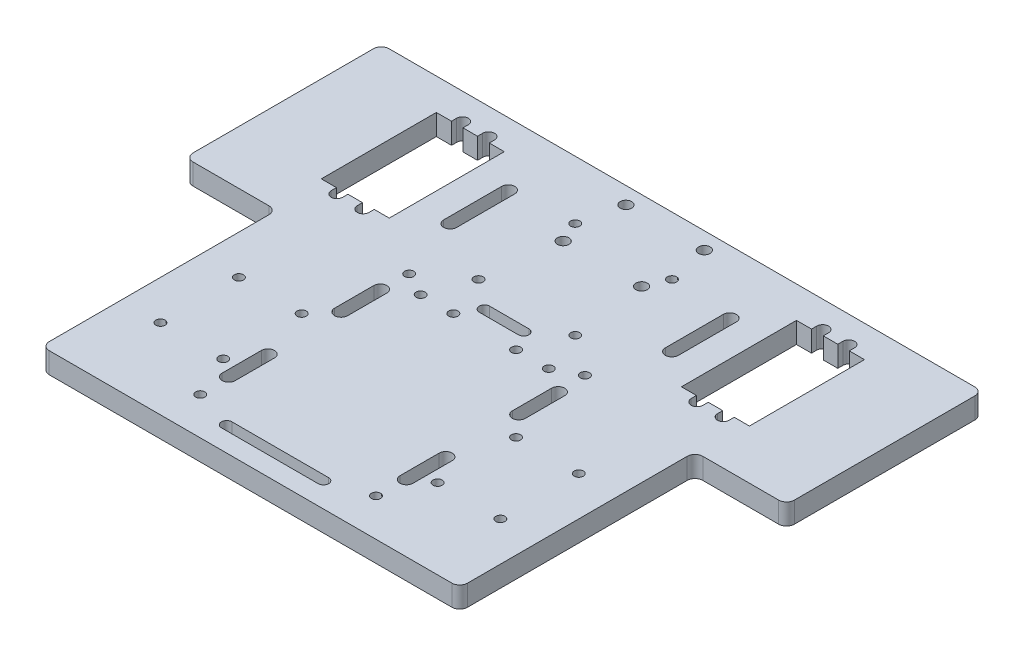
SolidWorks part; units mm, degrees
ref_plane "前视基准面" through (0, 0, 0) normal (0, 0, 1) x (1, 0, 0)
ref_plane "上视基准面" through (0, 0, 0) normal (0, 1, 0) x (1, 0, 0)
ref_plane "右视基准面" through (0, 0, 0) normal (1, 0, 0) x (0, 0, -1)
other "Configuration Table"
sketch "草图1" plane through (0, 0, 0) normal (0, 1, 0) x (1, 0, 0)
  line L1 (115, -130.4648) -> (-115, -130.4648)
  line L2 (115, -130.4648) -> (115, 69.5352)
  line L3 (115, 69.5352) -> (-115, 69.5352)
  line L4 (-115, -130.4648) -> (-115, 69.5352)
  line L5 (115, -130.4648) -> (-115, 69.5352) construction
  line L6 (115, 69.5352) -> (-115, -130.4648) construction
  point P0 (0, -30.4648)
  dimension "D1" = 230
  dimension "D2" = 200
extrude "凸台-拉伸1" add sketch "草图1" along normal blind 8
sketch "草图2" plane through (0, 0, 0) normal (0, 1, 0) x (1, 0, 0)
  line L0 (0, 0) -> (0, -142.6285) construction
  line L1 (33.6, -116.0917) -> (-33.6, -116.0917)
  line L2 (33.6, -116.0917) -> (33.6, -36.1917)
  line L3 (33.6, -36.1917) -> (-33.6, -36.1917)
  line L4 (-33.6, -116.0917) -> (-33.6, -36.1917)
  line L5 (33.6, -116.0917) -> (-33.6, -36.1917) construction
  line L6 (33.6, -36.1917) -> (-33.6, -116.0917) construction
  line L7 (-80, -130.4648) -> (-115, -130.4648)
  line L12 (-80, -130.4648) -> (-80, -40.4648)
  line L13 (-115, -130.4648) -> (-115, -40.4648)
  line L14 (-65, -69.9176) -> (-41, -69.9176)
  line L15 (0, -40.8981) -> (-12, -40.8981)
  line L16 (-12, -40.8981) -> (-24.5, -40.8981)
  line L17 (-73.8742, 24.4667) -> (-73.8742, -23.5333) construction
  line L18 (18.5, -24.7805) -> (-18.5, -24.7805)
  line L19 (18.5, -24.7805) -> (18.5, 12.2195)
  line L20 (18.5, 12.2195) -> (-18.5, 12.2195)
  line L21 (-18.5, -24.7805) -> (-18.5, 12.2195)
  line L22 (18.5, -24.7805) -> (-18.5, 12.2195) construction
  line L23 (18.5, 12.2195) -> (-18.5, -24.7805) construction
  line L24 (-55.8742, -21.5333) -> (-81.8742, -21.5333)
  line L25 (-55.8742, -21.5333) -> (-55.8742, 22.4667)
  line L26 (-55.8742, 22.4667) -> (-81.8742, 22.4667)
  line L27 (-81.8742, -21.5333) -> (-81.8742, 22.4667)
  line L28 (-55.8742, -21.5333) -> (-81.8742, 22.4667) construction
  line L29 (-55.8742, 22.4667) -> (-81.8742, -21.5333) construction
  line L30 (-63.8742, -23.5333) -> (-73.8742, -23.5333)
  line L31 (-63.8742, -23.5333) -> (-63.8742, 24.4667)
  line L32 (-63.8742, 24.4667) -> (-73.8742, 24.4667)
  line L33 (-73.8742, -23.5333) -> (-73.8742, 24.4667)
  line L34 (-63.8742, -23.5333) -> (-73.8742, 24.4667) construction
  line L35 (-63.8742, 24.4667) -> (-73.8742, -23.5333) construction
  line L38 (-71.6742, 24.4667) -> (-71.6742, -23.5333)
  line L41 (55.8742, -21.5333) -> (81.8742, -21.5333)
  line L42 (55.8742, -21.5333) -> (55.8742, 22.4667)
  line L43 (55.8742, 22.4667) -> (81.8742, 22.4667)
  line L44 (81.8742, -21.5333) -> (81.8742, 22.4667)
  line L45 (63.8742, 24.4667) -> (63.8742, -23.5333) construction
  line L48 (61.6242, 24.4667) -> (61.6242, -23.5333)
  line L51 (-76.0742, 24.4667) -> (-76.0742, -23.5333)
  line L52 (15, 4.1019) -> (-15, 4.1019)
  line L53 (15, 4.1019) -> (15, 28.1019)
  line L54 (15, 28.1019) -> (-15, 28.1019)
  line L55 (-15, 4.1019) -> (-15, 28.1019)
  line L56 (15, 4.1019) -> (-15, 28.1019) construction
  line L57 (15, 28.1019) -> (-15, 4.1019) construction
  line L60 (-18.5, -121.0937) -> (18.5, -121.0937) construction
  line L61 (-18.5, -119.0937) -> (18.5, -119.0937)
  line L62 (-18.5, -123.0937) -> (18.5, -123.0937)
  line L63 (-63.8742, 24.4667) -> (-63.8742, -23.5333) construction
  line L64 (-61.6242, 24.4667) -> (-61.6242, -23.5333)
  line L65 (-66.1242, 24.4667) -> (-66.1242, -23.5333)
  line L66 (66.1242, 24.4667) -> (66.1242, -23.5333)
  line L67 (73.8742, 24.4667) -> (73.8742, -23.5333) construction
  line L68 (71.6742, 24.4667) -> (71.6742, -23.5333)
  line L69 (76.0742, 24.4667) -> (76.0742, -23.5333)
  line L70 (-80, -40.4648) -> (-115, -40.4648)
  line L71 (-65, -69.9176) -> (-41, -69.9176)
  line L72 (-65, -69.9176) -> (-65, -99.9176)
  line L73 (-41, -69.9176) -> (-41, -99.9176)
  line L74 (-65, -99.9176) -> (-41, -99.9176)
  line L75 (-115, -130.4648) -> (115, -130.4648) construction
  line L76 (80, -130.4648) -> (80, -40.4648)
  line L77 (80, -130.4648) -> (115, -130.4648)
  line L78 (115, -130.4648) -> (115, -40.4648)
  line L79 (80, -40.4648) -> (115, -40.4648)
  circle A0 centre (-33.6, -36.1917) radius 1.75
  circle A1 centre (33.6, -36.1917) radius 1.75
  circle A2 centre (-33.6, -116.0917) radius 1.75
  circle A3 centre (33.6, -116.0917) radius 1.75
  circle A4 centre (-41, -69.9176) radius 1.75
  circle A5 centre (-41, -99.9176) radius 1.75
  circle A6 centre (-65, -99.9176) radius 1.75
  circle A7 centre (-65, -69.9176) radius 1.75
  circle A8 centre (-24.5, -40.8981) radius 1.75
  circle A9 centre (-12, -40.8981) radius 1.75
  circle A10 centre (-18.5, 12.2195) radius 1.75
  circle A11 centre (18.5, 12.2195) radius 1.75
  circle A12 centre (18.5, -24.7805) radius 1.75
  circle A13 centre (-18.5, -24.7805) radius 1.75
  circle A18 centre (24.5, -40.8981) radius 1.75
  circle A19 centre (12, -40.8981) radius 1.75
  circle A20 centre (41, -69.9176) radius 1.75
  circle A21 centre (41, -99.9176) radius 1.75
  circle A22 centre (65, -99.9176) radius 1.75
  circle A23 centre (65, -69.9176) radius 1.75
  circle A28 centre (-15, 28.1019) radius 2.2
  circle A29 centre (-15, 4.1019) radius 2.2
  circle A30 centre (15, 28.1019) radius 2.2
  circle A31 centre (15, 4.1019) radius 2.2
  arc A34 (-18.5, -119.0937) -> (-18.5, -123.0937) centre (-18.5, -121.0937) ccw
  arc A35 (18.5, -123.0937) -> (18.5, -119.0937) centre (18.5, -121.0937) ccw
  arc A36 (-71.6742, 24.4667) -> (-76.0742, 24.4667) centre (-73.8742, 24.4667) ccw
  arc A37 (-76.0742, -23.5333) -> (-71.6742, -23.5333) centre (-73.8742, -23.5333) ccw
  arc A38 (-61.6242, 24.4667) -> (-66.1242, 24.4667) centre (-63.8742, 24.4667) ccw
  arc A39 (-66.1242, -23.5333) -> (-61.6242, -23.5333) centre (-63.8742, -23.5333) ccw
  arc A40 (61.6242, 24.4667) -> (66.1242, 24.4667) centre (63.8742, 24.4667) cw
  arc A41 (66.1242, -23.5333) -> (61.6242, -23.5333) centre (63.8742, -23.5333) cw
  arc A42 (71.6742, 24.4667) -> (76.0742, 24.4667) centre (73.8742, 24.4667) cw
  arc A43 (76.0742, -23.5333) -> (71.6742, -23.5333) centre (73.8742, -23.5333) cw
  point P0 (0, -76.1417)
  point P31 (0, 0)
  point P34 (0, -6.2805)
  point P40 (-68.8742, 0.4667)
  point P49 (0, -6.2805)
  point P52 (-73.8742, 0.4667)
  point P53 (-68.8742, 0.4667)
  point P62 (-63.8742, 0.4667)
  point P85 (63.8742, 0.4667)
  point P92 (73.8742, 0.4667)
  point P97 (0, 16.1019)
  point P106 (0, 0)
  point P108 (0, 0)
  point P110 (0, 0)
  point P111 (0, 0)
  point P112 (0, 0)
  point P113 (0, -121.0937)
  point P121 (0, 0)
  point P122 (0, 0)
  point P123 (0, 0)
  point P124 (0, 0)
  point P125 (0, 0)
  point P126 (0, 0)
  point P127 (0, 0)
  point P128 (0, 0)
  point P129 (0, 0)
  dimension "D3" = 35
  dimension "D6" = 37
  dimension "D8" = 4
  dimension "D13" = 30
  dimension "D15" = 30
  dimension "D1" = 67.2
  dimension "D2" = 79.9
  dimension "D4" = 90
  dimension "D7" = 37
  dimension "D9" = 44
  dimension "D10" = 26
  dimension "D11" = 48
  dimension "D12" = 10
  dimension "D14" = 24
extrude "切除-拉伸2" cut sketch "草图2" along normal blind 8 contours L27 L26 L25 L24 | A28 | A29 | A31 | A30 | L42 L43 L44 L41 | L68 A43 L69 A42 | L48 A41 L66 A40 | A4 | A7 | A6 | A5 | A13 | A12 | A19 | A18 | A11 | A10 | A9 | A8 | A0 | A1 | A2 | A3 | L61 A35 L62 A34 | A21 | A22 | A23 | A20
extrude "切除-拉伸3" cut sketch "草图2<3>" along normal blind 8 contours A36 L51 A37 L38 | A38 L65 A39 L64 | A40 L66 A41 L48 | A42 L69 A43 L68
sketch "草图2<3>" plane through (0, 0, 0) normal (0, 1, 0) x (1, 0, 0) same geometry as "草图2"
sketch "草图3" plane through (0, 0, 0) normal (0, 1, 0) x (1, 0, 0)
  line L0 (-42.3858, 10.4742) -> (-42.3858, -11.7168) construction
  line L1 (-39.8858, 10.4742) -> (-39.8858, -11.7168)
  line L2 (-44.8858, 10.4742) -> (-44.8858, -11.7168)
  line L3 (0, 0) -> (0, -150.4011) construction
  line L4 (42.3858, 10.4742) -> (42.3858, -11.7168) construction
  line L5 (39.8858, 10.4742) -> (39.8858, -11.7168)
  line L6 (44.8858, 10.4742) -> (44.8858, -11.7168)
  line L7 (-34, -104.8187) -> (-34, -89.8187) construction
  line L8 (34, -104.8187) -> (-34, -104.8187)
  line L9 (34, -104.8187) -> (34, -46.8187)
  line L10 (34, -46.8187) -> (-34, -46.8187)
  line L11 (-34, -104.8187) -> (-34, -46.8187)
  line L12 (34, -104.8187) -> (-34, -46.8187) construction
  line L13 (34, -46.8187) -> (-34, -104.8187) construction
  line L14 (-36.5, -104.8187) -> (-36.5, -89.8187)
  line L15 (-31.5, -104.8187) -> (-31.5, -89.8187)
  line L16 (-34, -46.8187) -> (-34, -61.8187) construction
  line L19 (-31.5, -46.8187) -> (-31.5, -61.8187)
  line L20 (-36.5, -46.8187) -> (-36.5, -61.8187)
  line L21 (34, -104.8187) -> (34, -89.8187) construction
  line L22 (36.5, -104.8187) -> (36.5, -89.8187)
  line L23 (31.5, -104.8187) -> (31.5, -89.8187)
  line L24 (34, -46.8187) -> (34, -61.8187) construction
  line L25 (31.5, -46.8187) -> (31.5, -61.8187)
  line L26 (36.5, -46.8187) -> (36.5, -61.8187)
  line L27 (-7.5, -33.5004) -> (7.5, -33.5004) construction
  line L28 (-7.5, -31.5004) -> (7.5, -31.5004)
  line L29 (-7.5, -35.5004) -> (7.5, -35.5004)
  arc A0 (-39.8858, 10.4742) -> (-44.8858, 10.4742) centre (-42.3858, 10.4742) ccw
  arc A1 (-44.8858, -11.7168) -> (-39.8858, -11.7168) centre (-42.3858, -11.7168) ccw
  arc A2 (39.8858, 10.4742) -> (44.8858, 10.4742) centre (42.3858, 10.4742) cw
  arc A3 (44.8858, -11.7168) -> (39.8858, -11.7168) centre (42.3858, -11.7168) cw
  arc A8 (-36.5, -104.8187) -> (-31.5, -104.8187) centre (-34, -104.8187) ccw
  arc A9 (-31.5, -89.8187) -> (-36.5, -89.8187) centre (-34, -89.8187) ccw
  arc A12 (-31.5, -46.8187) -> (-36.5, -46.8187) centre (-34, -46.8187) ccw
  arc A13 (-36.5, -61.8187) -> (-31.5, -61.8187) centre (-34, -61.8187) ccw
  arc A14 (36.5, -104.8187) -> (31.5, -104.8187) centre (34, -104.8187) cw
  arc A15 (31.5, -89.8187) -> (36.5, -89.8187) centre (34, -89.8187) cw
  arc A16 (31.5, -46.8187) -> (36.5, -46.8187) centre (34, -46.8187) cw
  arc A17 (36.5, -61.8187) -> (31.5, -61.8187) centre (34, -61.8187) cw
  arc A18 (-7.5, -31.5004) -> (-7.5, -35.5004) centre (-7.5, -33.5004) ccw
  arc A19 (7.5, -35.5004) -> (7.5, -31.5004) centre (7.5, -33.5004) ccw
  point P2 (-42.3858, -0.6213)
  point P10 (-34, -97.3187)
  point P14 (42.3858, -0.6213)
  point P19 (0, -75.8187)
  point P29 (-34, -54.3187)
  point P36 (34, -97.3187)
  point P42 (34, -54.3187)
  point P48 (0, -33.5004)
  point P53 (-42.9173, 15.6566)
  point P54 (-42.7844, -11.7168)
  point P55 (-42.3858, 10.4742)
  dimension "D1" = 68
  dimension "D2" = 58
extrude "切除-拉伸5" cut sketch "草图3" along normal blind 8 contours L1 A1 L2 A0 | L5 A3 L6 A2
extrude "切除-拉伸6" cut sketch "草图3<5>" along normal blind 8 contours L19 A13 L20 A12 | L25 A17 L26 A16 | L15 A9 L14 A8 | L23 A15 L22 A14
sketch "草图3<5>" plane through (0, 0, 0) normal (0, 1, 0) x (1, 0, 0) same geometry as "草图3"
extrude "切除-拉伸7" cut sketch "草图3<6>" along normal blind 8 contours L29 A19 L28 A18
sketch "草图3<6>" plane through (0, 0, 0) normal (0, 1, 0) x (1, 0, 0) same geometry as "草图3"
extrude "切除-拉伸10" cut sketch "草图2<5>" along normal blind 8 contours L12 L70 L13 L7 | L79 L76 L77 L78 region at (-97.5, 0, 85.4648) region at (97.5, 0, 85.4648)
sketch "草图2<5>" plane through (0, 0, 0) normal (0, 1, 0) x (1, 0, 0) same geometry as "草图2"
sketch "草图4" plane through (0, 0, 0) normal (0, 1, 0) x (1, 0, 0)
  line L0 (-115, 69.5352) -> (-115, 34.5352)
  line L1 (-115, 69.5352) -> (115, 69.5352)
  line L2 (-115, 34.5352) -> (115, 34.5352)
  line L3 (115, 69.5352) -> (115, 34.5352)
  line L4 (-115, 69.5352) -> (-115, -40.4648) construction
  dimension "D1" = 35
  dimension "D2" = 230
extrude "切除-拉伸12" cut sketch "草图4" along normal blind 8 contours L0 L1 L3 L2
fillet "圆角1" radius 3 8 edges at (115, 4, -34.5352) (115, 4, 40.4648) (80, 4, 40.4648) (80, 4, 130.4648) (-80, 4, 130.4648) (-80, 4, 40.4648) (-115, 4, 40.4648) (-115, 4, -34.5352)
